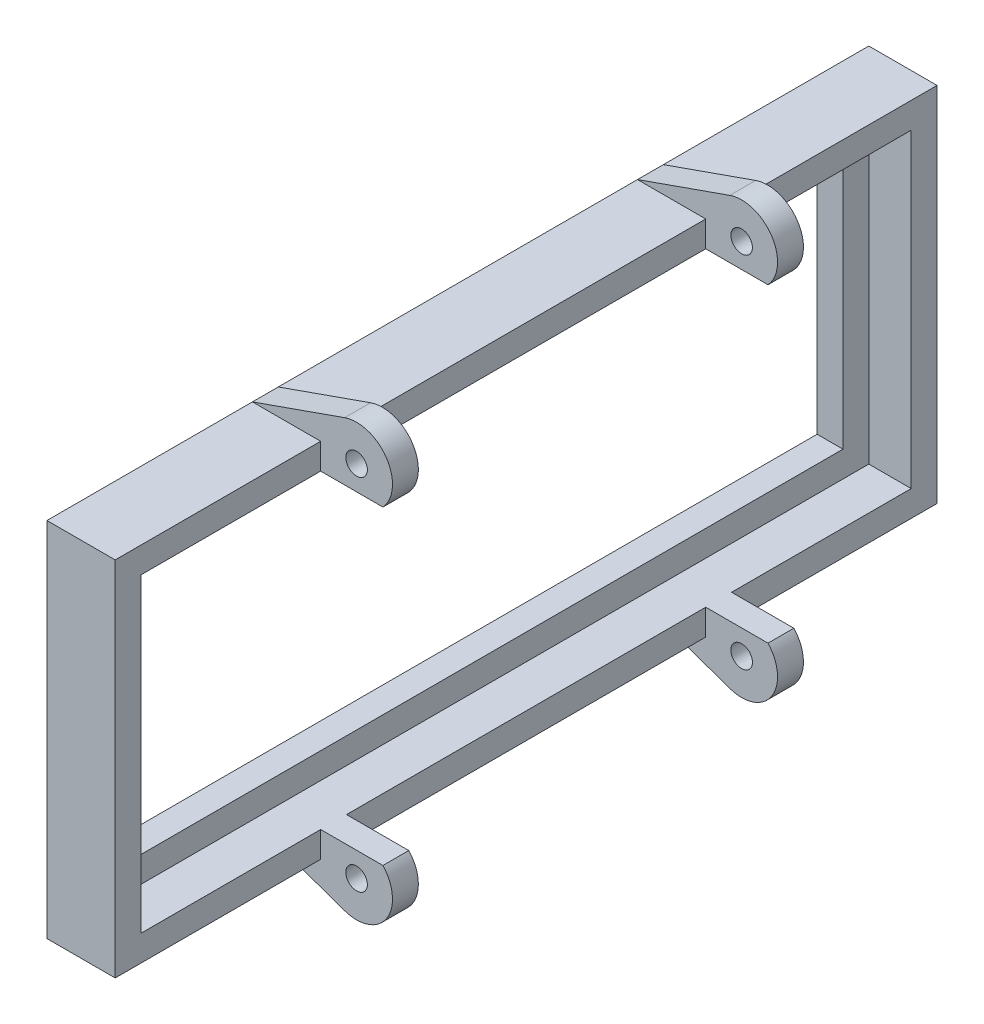
SolidWorks part; units mm, degrees
ref_plane "前视基准面" through (0, 0, 0) normal (0, 0, 1) x (1, 0, 0)
ref_plane "上视基准面" through (0, 0, 0) normal (0, 1, 0) x (1, 0, 0)
ref_plane "右视基准面" through (0, 0, 0) normal (1, 0, 0) x (0, 0, -1)
sketch "草图1" plane through (0, 0, 0) normal (1, 0, 0) x (0, 0, -1)
  line L1 (-50, 18) -> (50, 18)
  line L2 (-50, 18) -> (-50, -18)
  line L3 (-50, -18) -> (50, -18)
  line L4 (50, 18) -> (50, -18)
  line L5 (-53.6, 21.6) -> (53.6, 21.6)
  line L6 (-53.6, 21.6) -> (-53.6, -21.6)
  line L7 (-53.6, -21.6) -> (53.6, -21.6)
  line L8 (53.6, 21.6) -> (53.6, -21.6)
  line L9 (-57.2, 25.2) -> (57.2, 25.2)
  line L10 (-57.2, 25.2) -> (-57.2, -25.2)
  line L11 (-57.2, -25.2) -> (57.2, -25.2)
  line L12 (57.2, 25.2) -> (57.2, -25.2)
  point P4 (-50, 0)
  point P5 (0, 18)
  point P11 (0, 21.6)
  point P12 (-53.6, 0)
  point P17 (-57.2, 0)
  point P18 (0, 25.2)
  dimension "D1" = 36
  dimension "D2" = 100
  dimension "D3" = 3.6
  dimension "D4" = 3.6
  dimension "D5" = 3.6
  dimension "D6" = 3.6
extrude "凸台-拉伸1" add sketch "草图1" along normal blind 3.6 contours L12 L9 L10 L11 L5 L8 L7 L6 | L8 L5 L6 L7 L1 L4 L3 L2 region at (0, 20.4442, 0) region at (0, 23.9499, 0)
extrude "凸台-拉伸2" add sketch "草图1<3>" along normal blind 9.5 contours L12 L9 L10 L11 L5 L8 L7 L6 region at (0, 23.9499, 0)
sketch "草图1<3>" plane through (0, 0, 0) normal (1, 0, 0) x (0, 0, -1) same geometry as "草图1"
sketch "草图2" plane through (0, 0, 0) normal (0, 0, 1) x (1, 0, 0)
  line L0 (3.6, -21.6) -> (3.6, 21.6) construction
  line L1 (12.8409, 29.7167) -> (0, 25.2)
  line L2 (0, 25.2) -> (0, 21.6)
  line L3 (0, 25.2) -> (0, -25.2) construction
  line L4 (0, 21.6) -> (9.5, 21.6)
  line L5 (9.5, 21.6) -> (18.1661, 21.6)
  circle A0 centre (14.5, 25) radius 1.5
  arc A1 (18.1661, 21.6) -> (12.8409, 29.7167) centre (14.5, 25) ccw
  point P3 (0, 0)
  point P8 (0, 0)
  point P16 (0, 0)
  point P17 (0, 0)
  point P18 (17.6055, 21.1)
  point P19 (-41.6736, 21.6662)
  point P20 (-37.6992, 7.9765)
  point P21 (-19.1242, -3.7812)
  point P22 (11.0321, 21.3981)
  point P23 (0, 0)
  point P24 (0, 0)
  point P25 (18.17, 21.6)
  point P26 (12.0407, 29.3533)
  dimension "D1" = 25
  dimension "D2" = 3
  dimension "D4" = 5
  dimension "D3" = 10.9
extrude "凸台-拉伸3" add sketch "草图2" along normal blind 3.6 from offset 25
mirror "镜向1" about plane through (0, 0, 0) normal (0, 0, 1) of "凸台-拉伸3"
mirror "镜向2" about plane through (0, 0, 0) normal (0, 1, 0) of "凸台-拉伸3", "镜向1"
